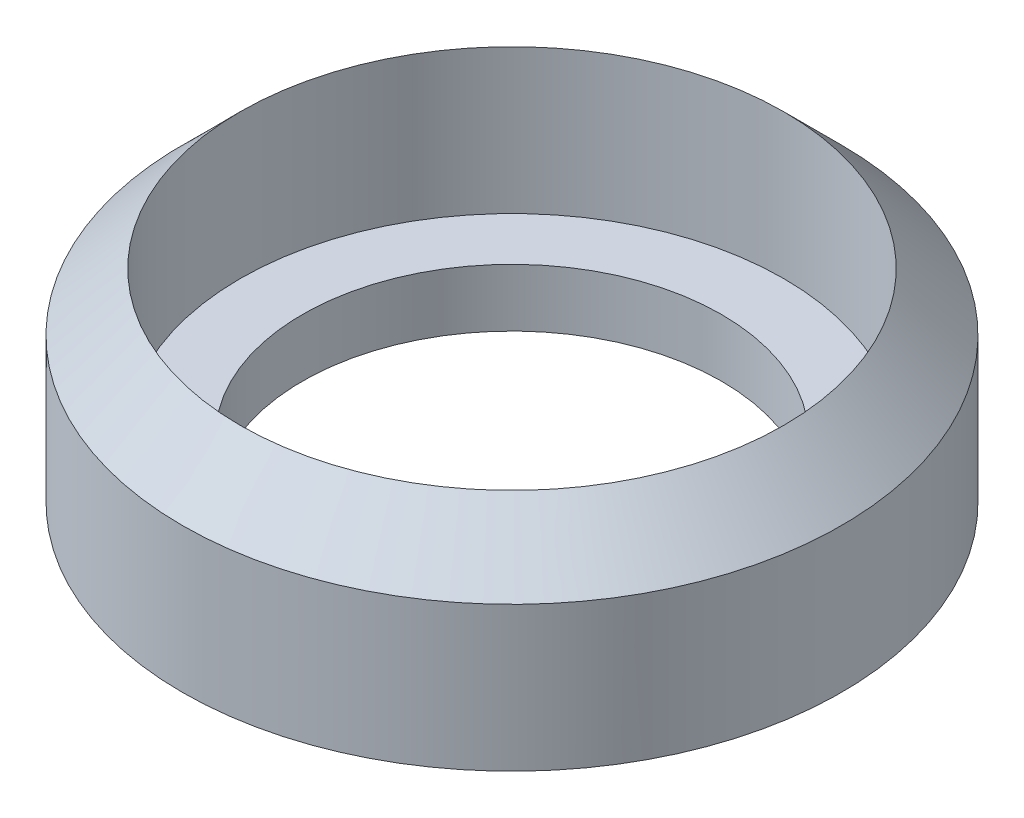
SolidWorks part; units mm, degrees
ref_plane "Front Plane" through (0, 0, 0) normal (0, 0, 1) x (1, 0, 0)
ref_plane "Top Plane" through (0, 0, 0) normal (0, 1, 0) x (1, 0, 0)
ref_plane "Right Plane" through (0, 0, 0) normal (1, 0, 0) x (0, 0, -1)
sketch "Sketch1" plane through (0, 0, 0) normal (0, 0, 1) x (1, 0, 0)
  line L6 (0, 630.2783) -> (0, -512.9833) construction
  line L7 (36.25, 0) -> (36.25, 10)
  line L9 (57, 0) -> (57, 35)
  line L11 (36.25, 0) -> (57, 0)
  line L13 (57, 35) -> (47, 35)
  line L14 (47, 35) -> (47, 10)
  line L15 (47, 10) -> (36.25, 10)
  dimension "D1" = 72.5
  dimension "D2" = 114
  dimension "D3" = 35
  dimension "D4" = 25
  dimension "D5" = 10
revolve "Revolve1" add sketch "Sketch1" angle 360 about L6
chamfer "Chamfer1" distance 10 angle 45 1 edges at (0, 35, 57)
